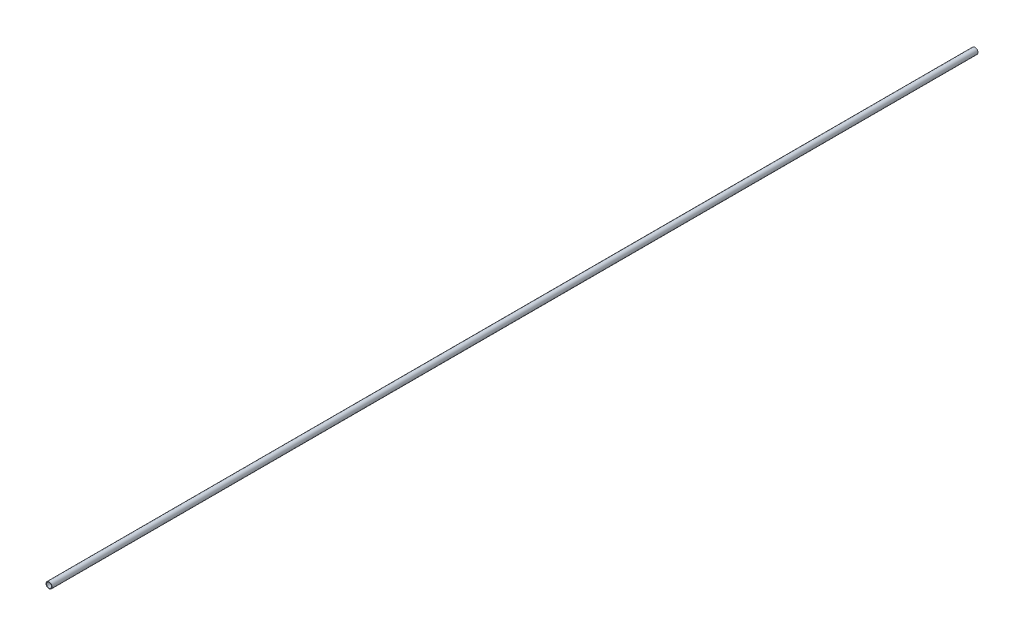
SolidWorks part; units mm, degrees
material "Thornel Mat VMA"
ref_plane "Front Plane" through (0, 0, 0) normal (0, 0, 1) x (1, 0, 0)
ref_plane "Top Plane" through (0, 0, 0) normal (0, 1, 0) x (1, 0, 0)
ref_plane "Right Plane" through (0, 0, 0) normal (1, 0, 0) x (0, 0, -1)
sketch "Sketch1" plane through (0, 0, 0) normal (0, 0, 1) x (1, 0, 0)
  circle A0 centre (0, 0) radius 3
  circle A1 centre (0, 0) radius 2.5
  dimension "D1" = 6
  dimension "D2" = 5
extrude "Boss-Extrude1" add sketch "Sketch1" along normal mid plane 914.4
